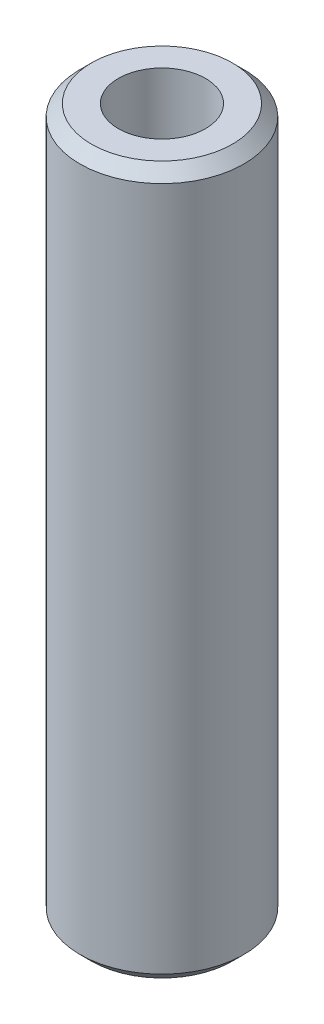
SolidWorks part; units mm, degrees
ref_plane "Front Plane" through (0, 0, 0) normal (0, 0, 1) x (1, 0, 0)
ref_plane "Top Plane" through (0, 0, 0) normal (0, 1, 0) x (1, 0, 0)
ref_plane "Right Plane" through (0, 0, 0) normal (1, 0, 0) x (0, 0, -1)
sketch "Sketch1" plane through (0, 0, 0) normal (0, 1, 0) x (1, 0, 0)
  circle A0 centre (0, 0) radius 15
  dimension "SHAFT_OD" = 30
extrude "Boss-Extrude1" add sketch "Sketch1" along normal blind 129.5476
sketch "Sketch2" plane through (0, 0, 0) normal (0, 1, 0) x (1, 0, 0)
  circle A0 centre (0, 0) radius 7.9809
  dimension "BORE_D" = 15.9617
extrude "Cut-Extrude1" cut sketch "Sketch2" along normal through all
chamfer "Chamfer1" distance 2.0977 angle 45 2 edges at (0, 129.5476, 15) (0, 0, 15)
